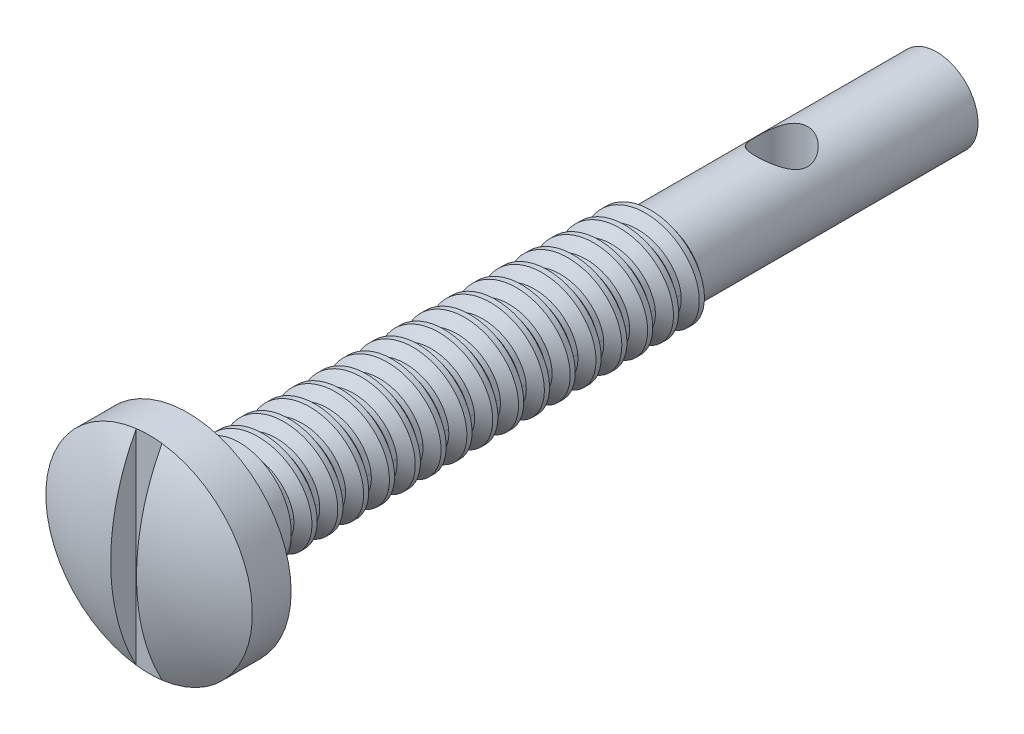
SolidWorks part; units mm, degrees
ref_plane "Front Plane" through (0, 0, 0) normal (0, 0, 1) x (1, 0, 0)
ref_plane "Top Plane" through (0, 0, 0) normal (0, 1, 0) x (1, 0, 0)
ref_plane "Right Plane" through (0, 0, 0) normal (1, 0, 0) x (0, 0, -1)
sketch "Main Body Sketch" plane through (0, 0, 0) normal (0, 0, 1) x (1, 0, 0)
  circle A0 centre (0, 0) radius 1.6
  dimension "D1" = 3.2
extrude "Main Body Extrude" add sketch "Main Body Sketch" against normal blind 29
sketch "Outer Body Sketch" plane through (0, 0, 0) normal (0, 0, 1) x (1, 0, 0)
  circle A0 centre (0, 0) radius 2
  dimension "D1" = 4
extrude "Outer Body Extrude" add sketch "Outer Body Sketch" against normal blind 2
ref_plane "Thread Plane" through (0, 0, -1) normal (0, 0, -1) x (-1, 0, 0)
sketch "Thread Base Sketch" plane through (0, 0, -1) normal (0, 0, -1) x (-1, 0, 0)
  circle A0 centre (0, 0) radius 1.6
  dimension "D1" = 3.2
curve "Thread helix" pitch 1 height 17 radius 1.6 centre (0, 0, -1) axis (0, 0, -1) start towards (-1, 0, 0)
sketch "Thread Shape Sketch" plane through (0, 0, 0) normal (0, 1, 0) x (1, 0, 0)
  line L0 (-1.6, 1.8) -> (-1.6, 1)
  line L4 (-1.6, 1.8) -> (-2, 1.5)
  line L5 (-2, 1.5) -> (-2, 1.3)
  line L6 (-2, 1.3) -> (-1.6, 1)
  dimension "D1" = 0.8
  dimension "D5" = 0.4
  dimension "D6" = 0.3
  dimension "D7" = 0.3
sweep "Thread Sweep" add profiles "Thread Shape Sketch" path "Thread helix"
sketch "Screw Head Sketch" plane through (0, 0, 0) normal (0, 0, 1) x (1, 0, 0)
  circle A0 centre (0, 0) radius 4
  dimension "D1" = 8
extrude "Screw Head Extrude" add sketch "Screw Head Sketch" along normal blind 1.5
dome "Screw Head Dome" faces to dome 1 distance 1 reverse direction no elliptical dome no face at (4, 0, 1.5) parameters "D1"=1
sketch "Screw Head Cut Sketch" plane through (0, 0, 0) normal (0, 1, 0) x (1, 0, 0)
  line L0 (-0.5, -1.5) -> (0.5, -1.5)
  line L1 (0.5, -1.5) -> (0.5, -2.5)
  line L2 (0.5, -2.5) -> (-0.5, -2.5)
  line L3 (-0.5, -2.5) -> (-0.5, -1.5)
  line L4 (4, -1.5) -> (-4, -1.5) construction
  dimension "D1" = 0.5
  dimension "D2" = 0.5
  dimension "D3" = 1
extrude "Screw Head Cut Extrude" cut sketch "Screw Head Cut Sketch" against normal up to next and the other way up to next
sketch "Pin Hole Sketch" plane through (0, 0, 0) normal (0, 1, 0) x (1, 0, 0)
  circle A0 centre (0, 23) radius 1
  dimension "D1" = 2
  dimension "D2" = 23
extrude "Pin Hole Extrude" cut sketch "Pin Hole Sketch" against normal up to next and the other way up to next
